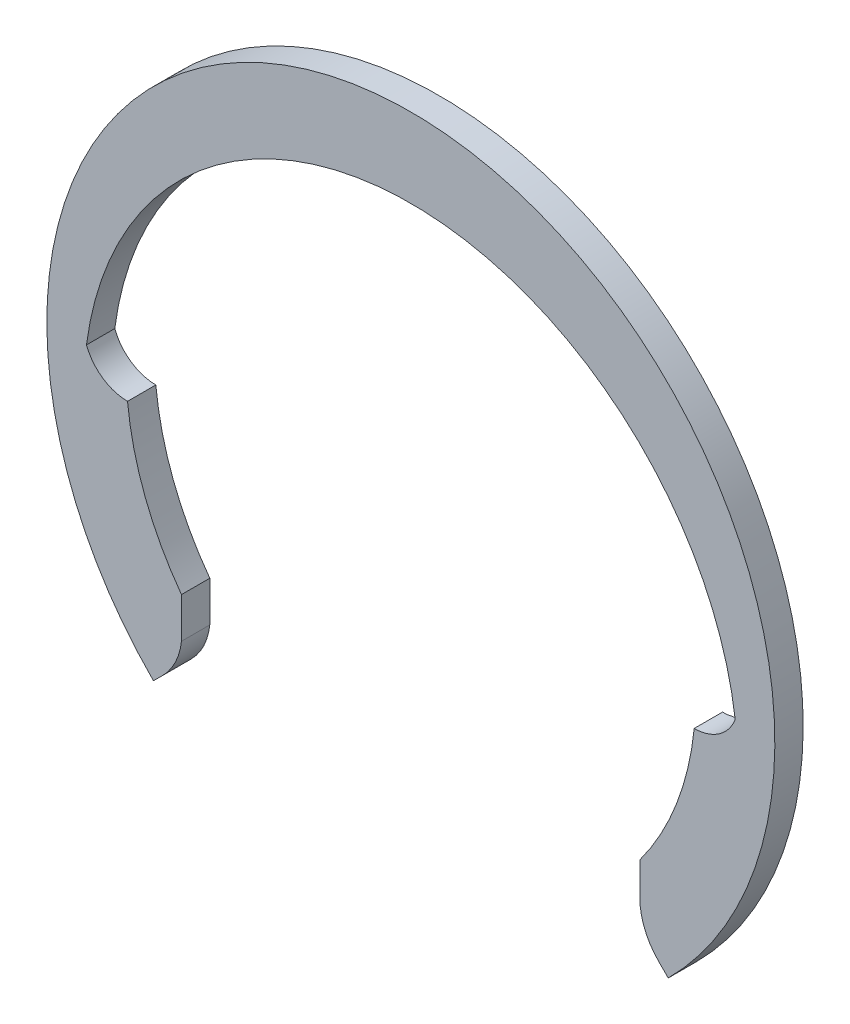
SolidWorks part; units mm, degrees
ref_plane "Front" through (0, 0, 0) normal (0, 0, 1) x (1, 0, 0)
ref_plane "Top" through (0, 0, 0) normal (0, 1, 0) x (1, 0, 0)
ref_plane "Right" through (0, 0, 0) normal (1, 0, 0) x (0, 0, -1)
sketch "Layout" plane through (0, 0, 0) normal (0, 0, 1) x (1, 0, 0)
  line L0 (0, 22.5) -> (0, -22.5) construction
  line L1 (-17.6, 0) -> (-22.5, 0) construction
  line L2 (-22.5, 0) -> (-24.25, 0) construction
  line L3 (-17.6, 0) -> (17.6, 0) construction
  line L4 (-14.1775, -14.1775) -> (-14.1775, -10.4287) construction
  line L5 (-17.5128, -1.75) -> (17.5128, -1.75) construction
  line L6 (-17.6, 0) -> (-17.6, -1.75) construction
  line L7 (0, 0) -> (-12.4451, -12.4451) construction
  line L8 (-12.4451, -12.4451) -> (-15.9099, -15.9099) construction
  circle A0 centre (0, 0) radius 22.5 construction
  circle A1 centre (0, 0) radius 17.6 construction
  arc A2 (0, 17.6) -> (-20.05, 0) centre (0, -2.6205) ccw construction
  circle A3 centre (0, 0) radius 22.9 construction
  arc A4 (-20.05, 0) -> (-17.5128, -1.75) centre (-17.5128, 0.9643) ccw construction
  dimension "D1" = 45
sketch "Sketch2" plane through (0, 0, 0) normal (0, 0, 1) x (1, 0, 0)
  line L0 (-14.1775, -14.1775) -> (-14.1775, -12.9279) construction
  line L1 (-14.1775, -12.9279) -> (-14.1775, -11.6783)
  line L2 (-14.1775, -11.6783) -> (-14.1775, -10.4287)
  line L4 (0, 22.5) -> (0, -22.5) construction
  line L5 (-14.1775, -14.1775) -> (-14.755, -14.755) construction
  line L6 (0, 22.5) -> (0, 17.6) construction
  line L7 (-14.755, -14.755) -> (-15.3324, -15.3324) construction
  line L8 (-15.3324, -15.3324) -> (-15.9099, -15.9099)
  line L9 (-12.4451, -12.4451) -> (-15.9099, -15.9099) construction
  line L10 (14.1775, -11.6783) -> (14.1775, -10.4287)
  line L11 (14.1775, -12.9279) -> (14.1775, -11.6783)
  line L12 (15.3324, -15.3324) -> (15.9099, -15.9099)
  circle A0 centre (0, 0) radius 22.5 construction
  arc A1 (0, 17.6) -> (-20.05, 0) centre (0, -2.6205) ccw construction
  arc A2 (-20.05, 0) -> (-17.5128, -1.75) centre (-17.5128, 0.9643) ccw construction
  circle A3 centre (0, 0) radius 17.6 construction
  arc A4 (15.9099, -15.9099) -> (-15.9099, -15.9099) centre (0, 0) ccw
  arc A5 (20.05, 0) -> (-20.05, 0) centre (0, -2.6205) ccw
  arc A6 (-20.05, 0) -> (-17.5128, -1.75) centre (-17.5128, 0.9643) ccw
  arc A7 (-17.5128, -1.75) -> (-14.1775, -10.4287) centre (0, 0) ccw
  arc A8 (-14.1775, -12.9279) -> (-15.3324, -15.3324) centre (-18.1796, -12.4852) cw
  arc A9 (14.1775, -12.9279) -> (15.3324, -15.3324) centre (18.1796, -12.4852) ccw
  arc A10 (17.5128, -1.75) -> (14.1775, -10.4287) centre (0, 0) cw
  arc A11 (20.05, 0) -> (17.5128, -1.75) centre (17.5128, 0.9643) cw
extrude "Boss-Extrude1" add sketch "Sketch2" along normal blind 1.75
ref_axis "Center Axis 1" [suppressed] through (0, 0, 1) along (0, 0, -1)
ref_plane "Contact Plane 1" [suppressed] through (0, 0, 1) normal (0, 0, 1) x (1, 0, 0)
ref_plane "Contact Plane 2" [suppressed] through (0, 0, 0) normal (0, 0, -1) x (-1, 0, 0)
equation "\"D1@Boss-Extrude1\"=\"thickness@Layout\""
